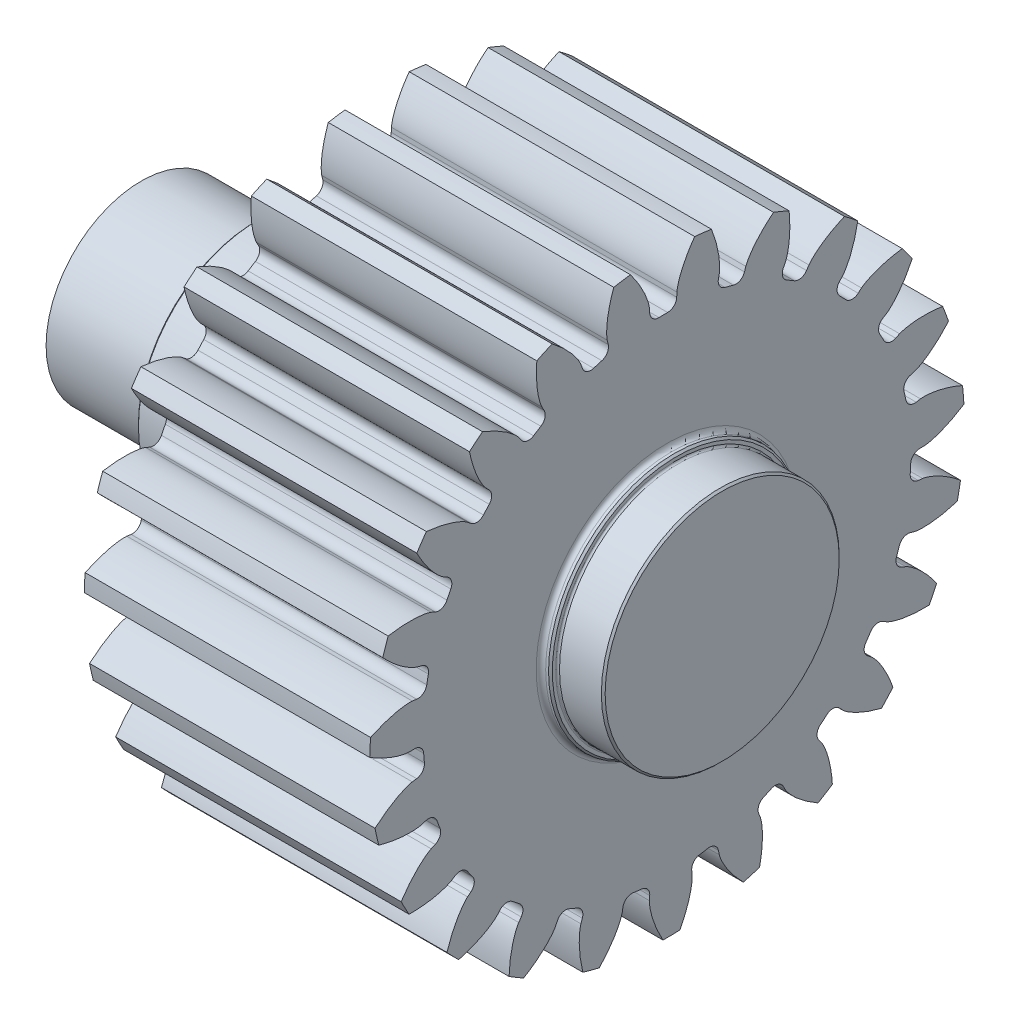
SolidWorks part; units mm, degrees
material "1.7225 (42CrMo4)"
ref_plane "前基準面" through (0, 0, 0) normal (0, 0, 1) x (1, 0, 0)
ref_plane "上基準面" through (0, 0, 0) normal (0, 1, 0) x (1, 0, 0)
ref_plane "右基準面" through (0, 0, 0) normal (1, 0, 0) x (0, 0, -1)
sketch "PitchDiameterRef" plane through (0, 0, 0) normal (1, 0, 0) x (0, 0, -1)
  circle A2 centre (0, 0) radius 28.75
  dimension "D1" = 57.5
sketch "ParametricInvoluteProfile" plane through (0, 0, 0) normal (1, 0, 0) x (0, 0, -1)
  spline S0 degree 4 poles (27.0162, 0) (27.0285, 0.0002) (27.063, 0.0014) (27.1283, 0.0062) (27.2345, 0.0176) (27.3694, 0.0372) (27.5431, 0.0686) (27.7467, 0.1133) (27.9692, 0.1703) (28.2097, 0.2409) (28.4481, 0.3188) (28.6843, 0.4035) (28.9181, 0.4941) (29.1993, 0.6113) (29.5336, 0.7619) (29.9198, 0.9526) (30.3521, 1.186) (30.786, 1.442) (31.2073, 1.7086) (31.6258, 1.9947) (32.0256, 2.2834) (32.4331, 2.5998) (32.8052, 2.9004) (33.2127, 3.2553) (33.5389, 3.547) (33.9586, 3.9505) (34.2034, 4.1944) (34.486, 4.4862) (34.6095, 4.6192) (34.6856, 4.701) knots 0 0 0 0 0 0.005377 0.015084 0.028532 0.04661 0.064855 0.092111 0.119476 0.146842 0.174209 0.201575 0.228941 0.256307 0.307035 0.361767 0.4165 0.471232 0.525964 0.580697 0.635429 0.690161 0.744894 0.799626 0.854358 0.909091 0.954545 1 1 1 1 1 construction
  spline S1 degree 4 poles (27.0162, 0) (27.0285, 0.0002) (27.063, 0.0014) (27.1283, 0.0062) (27.2345, 0.0176) (27.3694, 0.0372) (27.5431, 0.0686) (27.7467, 0.1133) (27.9692, 0.1703) (28.2097, 0.2409) (28.4481, 0.3188) (28.6843, 0.4035) (28.9181, 0.4941) (29.1993, 0.6113) (29.5336, 0.7619) (29.9198, 0.9526) (30.3521, 1.186) (30.786, 1.442) (31.2073, 1.7086) (31.6258, 1.9947) (32.0256, 2.2834) (32.4331, 2.5998) (32.8052, 2.9004) (33.2127, 3.2553) (33.5389, 3.547) (33.8676, 3.863) (34.0264, 4.019) (34.107, 4.0996) knots 0 0 0 0 0 0.005377 0.015084 0.028532 0.04661 0.064855 0.092111 0.119476 0.146842 0.174209 0.201575 0.228941 0.256307 0.307035 0.361767 0.4165 0.471232 0.525964 0.580697 0.635429 0.690161 0.744894 0.799626 0.854358 0.909091 0.909091 0.909091 0.909091 0.909091
sketch "Sketch4" plane through (0, 0, 0) normal (1, 0, 0) x (0, 0, -1)
  line L0 (0, 0) -> (22.0467, 0) construction
  line L1 (0, 0) -> (28.709, -1.5343) construction
  line L4 (27.0162, 0) -> (25.625, 0)
  line L5 (26.8623, -2.8794) -> (25.479, -2.7311)
  circle A4 centre (0, 0) radius 25.625
  circle A5 centre (0, 0) radius 27.0162
  arc A6 (28.709, -1.5343) -> (28.7468, 0.4285) centre (0, 0) ccw
  circle A7 centre (0, 0) radius 31.25
  spline S1 degree 4 poles (-12.4557, 2999.3672) (23.1098, 39.4632) (24.4791, 0.6167) (25.8797, -0.1273) (27.2345, 0.0176) (27.3694, 0.0372) (27.5431, 0.0686) (27.7467, 0.1133) (27.9692, 0.1703) (28.2097, 0.2409) (28.4481, 0.3188) (28.6843, 0.4035) (28.9181, 0.4941) (29.1993, 0.6113) (29.5336, 0.7619) (29.9198, 0.9526) (30.3521, 1.186) (30.786, 1.442) (31.2073, 1.7086) (31.6258, 1.9947) (32.0256, 2.2834) (32.4331, 2.5998) (32.8052, 2.9004) (33.2127, 3.2553) (34.8396, 4.7101) (39.7412, 9.974) (-23.2959, -52.3792) (2154.2897, 2126.1793) knots -0.547919 -0.547919 -0.547919 -0.547919 -0.547919 0.005377 0.015084 0.028532 0.04661 0.064855 0.092111 0.119476 0.146842 0.174209 0.201575 0.228941 0.256307 0.307035 0.361767 0.4165 0.471232 0.525964 0.580697 0.635429 0.690161 0.744894 0.799626 0.854358 1.782104 1.782104 1.782104 1.782104 1.782104 only from (27.0162, 0) to (34.107, 4.0996) construction
  spline S2 degree 4 poles (27.0162, 0) (27.0285, 0.0002) (27.063, 0.0014) (27.1283, 0.0062) (27.2345, 0.0176) (27.3694, 0.0372) (27.5431, 0.0686) (27.7467, 0.1133) (27.9692, 0.1703) (28.2097, 0.2409) (28.4481, 0.3188) (28.6843, 0.4035) (28.9181, 0.4941) (29.1993, 0.6113) (29.5336, 0.7619) (29.9198, 0.9526) (30.3521, 1.186) (30.786, 1.442) (31.2073, 1.7086) (31.6258, 1.9947) (32.0256, 2.2834) (32.4331, 2.5998) (32.8052, 2.9004) (33.2127, 3.2553) (33.5389, 3.547) (33.8676, 3.863) (34.0264, 4.019) (34.107, 4.0996) knots 0 0 0 0 0 0.005377 0.015084 0.028532 0.04661 0.064855 0.092111 0.119476 0.146842 0.174209 0.201575 0.228941 0.256307 0.307035 0.361767 0.4165 0.471232 0.525964 0.580697 0.635429 0.690161 0.744894 0.799626 0.854358 0.909091 0.909091 0.909091 0.909091 0.909091
  spline S4 degree 4 poles (26.8623, -2.8794) (26.8745, -2.8809) (26.9087, -2.8858) (26.9731, -2.8975) (27.0775, -2.9201) (27.2095, -2.954) (27.3789, -3.0038) (27.5766, -3.0698) (27.7918, -3.1503) (28.0234, -3.2461) (28.2521, -3.349) (28.478, -3.4584) (28.7007, -3.5734) (28.9678, -3.7198) (29.2842, -3.9052) (29.6479, -4.136) (30.0528, -4.4142) (30.457, -4.7149) (30.8474, -5.025) (31.233, -5.354) (31.5999, -5.6836) (31.9713, -6.0417) (32.3092, -6.3803) (32.6766, -6.7765) (32.9698, -7.1013) (33.263, -7.4506) (33.4042, -7.6226) (33.4758, -7.7114) knots 0 0 0 0 0 0.005377 0.015084 0.028532 0.04661 0.064855 0.092111 0.119476 0.146842 0.174209 0.201575 0.228941 0.256307 0.307035 0.361767 0.4165 0.471232 0.525964 0.580697 0.635429 0.690161 0.744894 0.799626 0.854358 0.909091 0.909091 0.909091 0.909091 0.909091
  dimension "D1" = 62.5
  dimension "D2" = 57.5
  dimension "D3" = 54.0323
  dimension "D4" = 51.25
  dimension "D5" = 1.9635
sketch "Sketch5" plane through (0, 0, 0) normal (1, 0, 0) x (0, 0, -1)
  circle A2 centre (0, 0) radius 31.25 construction
  circle A3 centre (0, 0) radius 31.25
extrude "Boss-Extrude1" add sketch "Sketch5" along normal blind 30
sketch "Sketch8" plane through (30, 0, 0) normal (1, 0, 0) x (0, 0, -1)
  line L0 (27.0162, 0) -> (25.625, 0) construction
  line L1 (26.8623, -2.8794) -> (25.479, -2.7311) construction
  line L2 (27.0162, 0) -> (25.625, 0)
  line L3 (26.8623, -2.8794) -> (25.479, -2.7311)
  circle A0 centre (0, 0) radius 25.625 construction
  circle A1 centre (0, 0) radius 31.25 construction
  arc A2 (25.479, -2.7311) -> (25.625, 0) centre (0, 0) ccw
  arc A3 (30.8431, -5.0262) -> (31.2032, 1.7104) centre (0, 0) ccw
  spline S0 degree 4 poles (11.8595, 999.8403) (24.091, 17.6208) (25.1288, 0.3173) (26.1866, -0.0945) (27.2345, 0.0176) (27.3694, 0.0372) (27.5431, 0.0686) (27.7467, 0.1133) (27.9692, 0.1703) (28.2097, 0.2409) (28.4481, 0.3188) (28.6843, 0.4035) (28.9181, 0.4941) (29.1993, 0.6113) (29.5336, 0.7619) (29.9198, 0.9526) (30.3521, 1.186) (30.786, 1.442) (31.2073, 1.7086) (31.6258, 1.9947) (32.0256, 2.2834) (32.4331, 2.5998) (32.8052, 2.9004) (33.2127, 3.2553) (34.5162, 4.4209) (37.837, 7.9411) (9.3324, -20.1528) (740.6444, 711.7303) knots -0.413254 -0.413254 -0.413254 -0.413254 -0.413254 0.005377 0.015084 0.028532 0.04661 0.064855 0.092111 0.119476 0.146842 0.174209 0.201575 0.228941 0.256307 0.307035 0.361767 0.4165 0.471232 0.525964 0.580697 0.635429 0.690161 0.744894 0.799626 0.854358 1.565081 1.565081 1.565081 1.565081 1.565081 only from (27.0162, 0) to (26.1486, 3.4643) construction
  spline S1 degree 4 poles (-94.7704, -995.4094) (22.0758, -20.088) (24.9518, -2.9937) (26.0475, -2.697) (27.0775, -2.9201) (27.2095, -2.954) (27.3789, -3.0038) (27.5766, -3.0698) (27.7918, -3.1503) (28.0234, -3.2461) (28.2521, -3.349) (28.478, -3.4584) (28.7007, -3.5734) (28.9678, -3.7198) (29.2842, -3.9052) (29.6479, -4.136) (30.0528, -4.4142) (30.457, -4.7149) (30.8474, -5.025) (31.233, -5.354) (31.5999, -5.6836) (31.9713, -6.0417) (32.3092, -6.3803) (32.6766, -6.7765) (33.8485, -8.0745) (36.7751, -11.9285) (11.4271, 19.0434) (660.5701, -786.6138) knots -0.413254 -0.413254 -0.413254 -0.413254 -0.413254 0.005377 0.015084 0.028532 0.04661 0.064855 0.092111 0.119476 0.146842 0.174209 0.201575 0.228941 0.256307 0.307035 0.361767 0.4165 0.471232 0.525964 0.580697 0.635429 0.690161 0.744894 0.799626 0.854358 1.565081 1.565081 1.565081 1.565081 1.565081 only from (26.8623, -2.8794) to (25.6305, -6.2315) construction
  spline S2 degree 4 poles (27.0162, 0) (27.0285, 0.0002) (27.063, 0.0014) (27.1283, 0.0062) (27.2345, 0.0176) (27.3694, 0.0372) (27.5431, 0.0686) (27.7467, 0.1133) (27.9692, 0.1703) (28.2097, 0.2409) (28.4481, 0.3188) (28.6843, 0.4035) (28.9181, 0.4941) (29.1993, 0.6113) (29.5336, 0.7619) (29.9198, 0.9526) (30.3521, 1.186) (30.7309, 1.4095) (30.9946, 1.5745) (31.1515, 1.6764) (31.2032, 1.7104) knots 0 0 0 0 0 0.005377 0.015084 0.028532 0.04661 0.064855 0.092111 0.119476 0.146842 0.174209 0.201575 0.228941 0.256307 0.307035 0.361767 0.4165 0.471232 0.498148 0.498148 0.498148 0.498148 0.498148
  spline S3 degree 4 poles (26.8623, -2.8794) (26.8745, -2.8809) (26.9087, -2.8858) (26.9731, -2.8975) (27.0775, -2.9201) (27.2095, -2.954) (27.3789, -3.0038) (27.5766, -3.0698) (27.7918, -3.1503) (28.0234, -3.2461) (28.2521, -3.349) (28.478, -3.4584) (28.7007, -3.5734) (28.9678, -3.7198) (29.2842, -3.9052) (29.6479, -4.136) (30.0528, -4.4142) (30.4056, -4.6767) (30.6503, -4.8689) (30.7954, -4.987) (30.8431, -5.0262) knots 0 0 0 0 0 0.005377 0.015084 0.028532 0.04661 0.064855 0.092111 0.119476 0.146842 0.174209 0.201575 0.228941 0.256307 0.307035 0.361767 0.4165 0.471232 0.498148 0.498148 0.498148 0.498148 0.498148
extrude "Cut-Extrude2" cut sketch "Sketch8" against normal up to surface (30 mm away) up to face at (0, 0, -31.25)
fillet "Fillet2" radius 0.95 2 edges at (15, -2.7311, -25.479) (15, 0, -25.625)
pattern_circular "CirPattern3" count 23 over 360 about axis through (30, 0, 0) along (-1, 0, 0) of "Cut-Extrude2", "Fillet2"
ref_axis "centerAxis" through (30, 0, 0) along (-1, 0, 0)
ref_plane "Plane1" through (-13.25, 0, 0) normal (-1, 0, 0) x (0, 0, 1)
sketch "Sketch12" plane through (0, 0, 0) normal (1, 0, 0) x (0, 0, -1)
  circle A0 centre (0, 0) radius 13.25
  dimension "D1" = 26.5
extrude "Boss-Extrude4" add sketch "Sketch12" against normal blind 1
sketch "Sketch10" plane through (-13.25, 0, 0) normal (-1, 0, 0) x (0, 0, 1)
  circle A0 centre (0, 0) radius 20
  circle A1 centre (0, 0) radius 12.5
  dimension "D1" = 40
  dimension "D2" = 25
extrude "Boss-Extrude2" add sketch "Sketch10" against normal up to body separate body contours A1 region at (-13.25, 0, 0)
sketch "Sketch11" plane through (0, 0, 0) normal (1, 0, 0) x (0, 0, -1)
  circle A0 centre (0, 0) radius 10
  dimension "D1" = 20
extrude "Boss-Extrude3" add sketch "Sketch11" against normal blind 12 from surface starting at face at (-13.25, 0, 12.5)
fillet "bearingHouseFillet" radius 0.2 1 edges at (-1, 0, -12.5)
chamfer "Chamfer1" distance 0.2 angle 45 1 edges at (-13.25, 0, 12.5)
fillet "Fillet4" radius 0.5 1 edges at (0, 0, -13.25)
sketch "Sketch14" plane through (-13.25, 0, 0) normal (-1, 0, 0) x (0, 0, 1)
  circle A0 centre (0, 0) radius 12.5
  circle A1 centre (0, 0) radius 13.25
  dimension "D1" = 25
  dimension "D2" = 26.5
extrude "Boss-Extrude5" add sketch "Sketch14" against normal blind 5.8 from surface contours A0 region at (-13.25, 0, 0) starting at face at (30, 0, 0)
extrude "Boss-Extrude6" add sketch "Sketch14<3>" against normal blind 1 from surface starting at face at (30, 0, -12.5)
sketch "Sketch14<3>" plane through (-13.25, 0, 0) normal (-1, 0, 0) x (0, 0, 1) same geometry as "Sketch14"
chamfer "Chamfer2" distance 0.2 angle 45 2 edges at (35.8, 0, -12.5) (31, 0, -13.25)
fillet "Fillet5" radius 0.2 1 edges at (31, 0, -12.5)
fillet "Fillet6" radius 0.5 1 edges at (30, 0, -13.25)
sketch "Sketch16" [suppressed] plane through (0, 0, 0) normal (0, 1, 0) x (1, 0, 0)
  line L0 (-25.25, 10) -> (-25.25, -10) construction
  line L6 (0, 0) -> (-25.25, 0) construction
  line L7 (-13.25, 11) -> (-13.25, -11) construction
  line L8 (-25.25, 2) -> (-13.25, 2)
  line L9 (-25.25, 2) -> (-25.25, 7)
  line L10 (-25.25, 7) -> (-13.25, 7)
  line L11 (-13.25, 2) -> (-13.25, 7)
  line L12 (-13.25, -2) -> (-13.25, -7)
  line L13 (-25.25, -7) -> (-13.25, -7)
  line L14 (-25.25, -2) -> (-25.25, -7)
  line L15 (-25.25, -2) -> (-13.25, -2)
  arc A0 (-13.25, 2) -> (-13.25, 7) centre (-13.25, 4.5) ccw
  arc A1 (-13.25, -2) -> (-13.25, -7) centre (-13.25, -4.5) cw
  dimension "D1" = 4
  dimension "D2" = 5
sketch "Sketch17" [suppressed] plane through (0, 0, 0) normal (1, 0, 0) x (0, 0, -1)
  line L0 (2, 9.798) -> (2, 7.448)
  line L2 (0, 0) -> (0, 10) construction
  circle A0 centre (0, 0) radius 10
  dimension "D1" = 20
  dimension "D2" = 4
  dimension "D3" = 2.35
extrude "Cut-Extrude3" [suppressed] cut sketch "Sketch16" along normal blind 5 from vertex contours L8 L11 L10 L9 | L11 A0 | L15 L14 L13 L12 | A1 L12
pattern_circular "CirPattern4" [suppressed] count 6 over 360 about axis through (30, 0, 0) along (-1, 0, 0) of bodies 114
ref_plane "Plane2" [suppressed] through (0, 0, 0) normal (0, 0.866, 0.5) x (-1, 0, 0)
sketch "Sketch18" [suppressed] plane through (0, 0, 0) normal (0, 0.866, 0.5) x (-1, 0, 0)
  line L0 (0, 0) -> (25.25, 0) construction
  line L1 (25.25, 1.9919) -> (25.25, 0) construction
  line L2 (25.25, 2) -> (13.25, 2)
  line L3 (25.25, 2) -> (25.25, -2)
  line L4 (25.25, -2) -> (13.25, -2)
  line L5 (13.25, 2) -> (13.25, -2)
  line L8 (13.25, 3.6763) -> (13.25, 1.9919) construction
  arc A0 (13.25, 2) -> (13.25, -2) centre (13.25, 0) ccw
  dimension "D1" = 4
extrude "Cut-Extrude4" [suppressed] cut sketch "Sketch18" along normal blind 5 from offset 7.91 contours L5 L0 L3 L2 | L0 L5 L4 L3 | L0 A0 L5 | A0 L0 L5
pattern_circular "CirPattern5" [suppressed] count 6 over 360 about axis through (30, 0, 0) along (-1, 0, 0) of bodies 116
equation "\"a\"= 20"
equation "\"M\"= 2.5"
equation "\"T\"= 23"
equation "\"R\"= 0.38 * \"M\""
equation "\"D\"= \"M\" * \"T\""
equation "\"Da\"= ( \"T\" + 2 ) * \"M\""
equation "\"Df\"= ( \"T\" - 2.5 ) * \"M\""
equation "\"Db\"= \"M\" * \"T\" * cos ( \"a\" )"
equation "\"rb\"= \"Db\" / 2"
equation "\"S\"= pi * \"M\" * 0.5"
equation "\"D1@Sketch4\"=\"Da\""
equation "\"D2@Sketch4\"=\"D\""
equation "\"D3@Sketch4\"=\"Db\""
equation "\"D4@Sketch4\"=\"Df\""
equation "\"D5@Sketch4\"=\"S\"/2"
equation "\"D1@Fillet2\"=\"R\""
equation "\"D1@CirPattern3\"=\"T\""
equation "\"input_a\"= 37.5"
equation "\"input_M\"= 1"
equation "\"input_T\"= 20"
equation "\"input_R\"= 0.38 * \"input_M\""
equation "\"input_D\"= \"input_M\" * \"input_T\""
equation "\"input_Df\"= ( \"input_T\" - 2.5 ) * \"input_M\""
equation "\"input_Db\"= \"input_M\" * \"input_T\" * cos ( \"input_a\" )"
equation "\"input_S\"= pi * \"input_M\" * 0.5"
equation "\"D1@PitchDiameterRef\"=\"D\""
